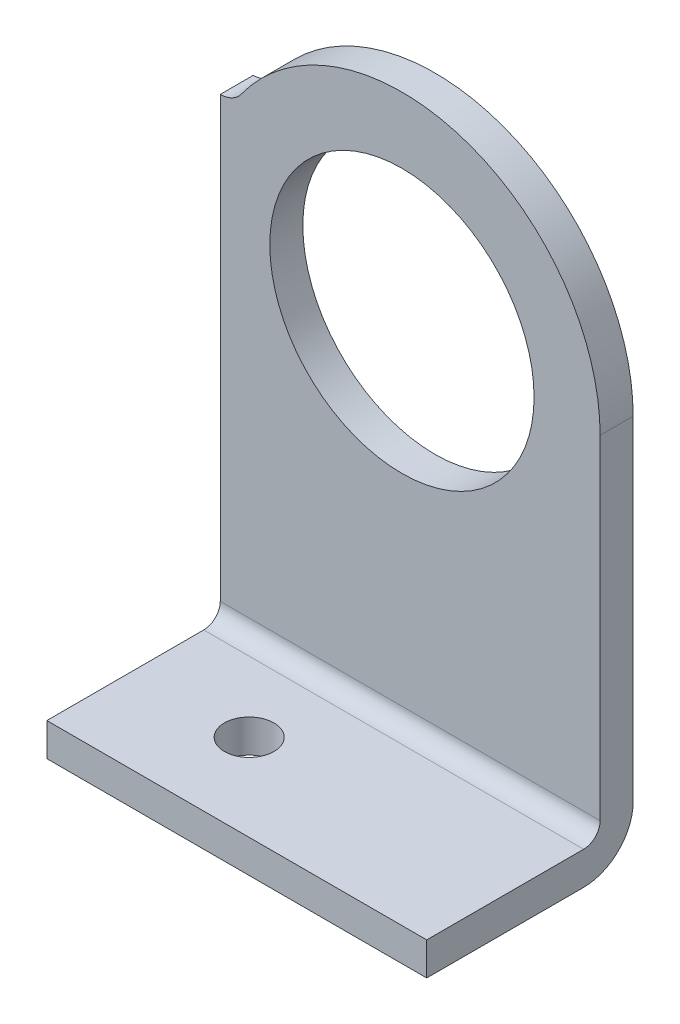
SolidWorks part; units mm, degrees
ref_plane "Front Plane" through (0, 0, 0) normal (0, 0, 1) x (1, 0, 0)
ref_plane "Top Plane" through (0, 0, 0) normal (0, 1, 0) x (1, 0, 0)
ref_plane "Right Plane" through (0, 0, 0) normal (1, 0, 0) x (0, 0, -1)
sketch "Sketch1" plane through (0, 0, 0) normal (0, 1, 0) x (1, 0, 0)
  line L1 (0, 0) -> (23, 0)
  line L2 (0, 0) -> (0, 12.5)
  line L3 (0, 12.5) -> (23, 12.5)
  line L4 (23, 0) -> (23, 12.5)
  dimension "D1" = 12.5
  dimension "D2" = 23
extrude "Boss-Extrude1" add sketch "Sketch1" along normal blind 2
sketch "Sketch2" plane through (0, 0, -12.5) normal (0, 0, -1) x (-1, 0, 0)
  line L1 (-23, 2) -> (0, 2)
  line L2 (-23, 2) -> (-23, 35.2062)
  line L3 (-23, 35.2062) -> (0, 35.2062)
  line L4 (0, 2) -> (0, 35.2062)
extrude "Boss-Extrude2" add sketch "Sketch2" against normal blind 2
sketch "Sketch3" plane through (0, 2, 0) normal (0, 1, 0) x (1, 0, 0)
  line L0 (0, 5.25) -> (23, 5.25) construction
  line L1 (0, 10.5) -> (0, 0) construction
  line L2 (23, 0) -> (23, 10.5) construction
  circle A0 centre (7, 5.25) radius 1.5
  dimension "D1" = 3
  dimension "D2" = 5.5
extrude "Cut-Extrude1" cut sketch "Sketch3" against normal blind 2 contours A0
sketch "Sketch4" plane through (0, 0, -12.5) normal (0, 0, -1) x (-1, 0, 0)
  line L1 (0, 35.2062) -> (0, 0) construction
  line L2 (0, 35.2062) -> (-23, 35.2062) construction
  circle A0 centre (-11, 23.2062) radius 8
  point P2 (-9.8668, 15.3728)
  point P3 (0, 0)
  point P4 (-10.1809, 18.5943)
  point P7 (-11, 20.2323)
  point P8 (0, 0)
  point P9 (-11, 19.1051)
  point P10 (-11, 20.214)
  dimension "D1" = 16
  dimension "D2" = 3
  dimension "D3" = 4
sketch "Sketch5" plane through (0, 0, -12.5) normal (0, 0, -1) x (-1, 0, 0)
sketch "Sketch6" plane through (0, 0, -12.5) normal (0, 0, -1) x (-1, 0, 0)
  line L0 (-23, 35.2062) -> (-23, 0) construction
  line L1 (0, 35.2062) -> (0, 0) construction
  arc A0 (-23, 23.2062) -> (-1.2728, 30.2334) centre (-11, 23.2062) cw
  arc A1 (-1.2728, 30.2334) -> (0, 29.5827) centre (0, 31.1529) ccw
extrude "Cut-Extrude2" cut sketch "Sketch4" against normal blind 2 contours A0
extrude "Cut-Extrude3" cut sketch "Sketch6" against normal blind 2 and the other way through all contours A0 A1
fillet "Fillet1" radius 3 1 edges at (11.5, 0, -12.5)
fillet "Fillet2" radius 1 1 edges at (11.5, 2, -10.5)
